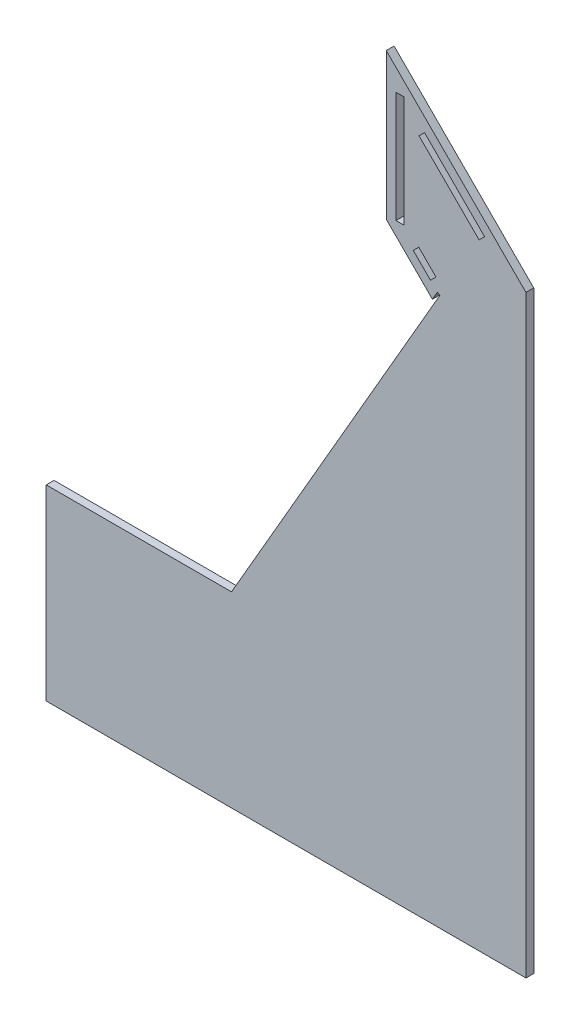
SolidWorks part; units mm, degrees
ref_plane "Front Plane" through (0, 0, 0) normal (0, 0, 1) x (1, 0, 0)
ref_plane "Top Plane" through (0, 0, 0) normal (0, 1, 0) x (1, 0, 0)
ref_plane "Right Plane" through (0, 0, 0) normal (1, 0, 0) x (0, 0, -1)
sketch "Sketch1" plane through (0, 0, 0) normal (0, 0, 1) x (1, 0, 0)
  line L0 (0, 192) -> (190, 192) construction
  line L1 (0, 0) -> (492, 0)
  line L2 (0, 0) -> (0, 192)
  line L3 (0, 192) -> (190, 192)
  line L5 (190, 192) -> (398.25, 552.6996)
  line L6 (398.25, 552.6996) -> (348.7525, 602.1971)
  line L7 (348.7525, 602.1971) -> (348.7525, 752.1971)
  line L8 (348.7525, 752.1971) -> (492, 608.9496)
  line L9 (492, 608.9496) -> (492, 0)
  line L13 (398.25, 552.6996) -> (403.7528, 562.2307)
  line L14 (403.7528, 562.2307) -> (401.1547, 563.7307)
  line L15 (401.1547, 563.7307) -> (396.0538, 554.8957)
  line L16 (191.1547, 200) -> (401.1547, 563.7307) construction
  line L17 (376.406, 588.4794) -> (394.0836, 570.8017) construction
  line L18 (394.0836, 570.8017) -> (399.7405, 576.4586) construction
  line L19 (399.7405, 576.4586) -> (382.0628, 594.1363) construction
  line L20 (382.0628, 594.1363) -> (376.406, 588.4794) construction
  line L29 (366.7283, 606.1571) -> (366.7283, 720.0871) construction
  line L30 (366.7283, 720.0871) -> (358.7283, 720.0871) construction
  line L31 (358.7283, 720.0871) -> (358.7283, 606.1571) construction
  line L32 (358.7283, 606.1571) -> (366.7283, 606.1571) construction
  line L33 (382.2846, 693.217) -> (443.9161, 631.5856) construction
  line L34 (443.9161, 631.5856) -> (449.5729, 637.2425) construction
  line L35 (449.5729, 637.2425) -> (387.9415, 698.8739) construction
  line L36 (387.9415, 698.8739) -> (382.2846, 693.217) construction
  line L37 (376.406, 588.4794) -> (394.0836, 570.8017)
  line L38 (394.0836, 570.8017) -> (399.7405, 576.4586)
  line L39 (399.7405, 576.4586) -> (382.0628, 594.1363)
  line L40 (382.0628, 594.1363) -> (376.406, 588.4794)
  line L41 (366.7283, 606.1571) -> (366.7283, 720.0871)
  line L42 (366.7283, 720.0871) -> (358.7283, 720.0871)
  line L43 (358.7283, 720.0871) -> (358.7283, 606.1571)
  line L44 (358.7283, 606.1571) -> (366.7283, 606.1571)
  line L45 (382.2846, 693.217) -> (443.9161, 631.5856)
  line L46 (443.9161, 631.5856) -> (449.5729, 637.2425)
  line L47 (449.5729, 637.2425) -> (387.9415, 698.8739)
  line L48 (387.9415, 698.8739) -> (382.2846, 693.217)
  dimension "D3" = 60
  dimension "D1" = 492
  dimension "D2" = 192
  dimension "D4" = 416.5
  dimension "D5" = 190
  dimension "D6" = 150
  dimension "D7" = 70
  dimension "D8" = 105
extrude "Boss-Extrude1" add sketch "Sketch1" along normal blind 8 contours L5 | L15 L14 L13 L5 L3 L2 L1 L9 L8 L7 L6 region at (314.4165, 236.9247, 0)
